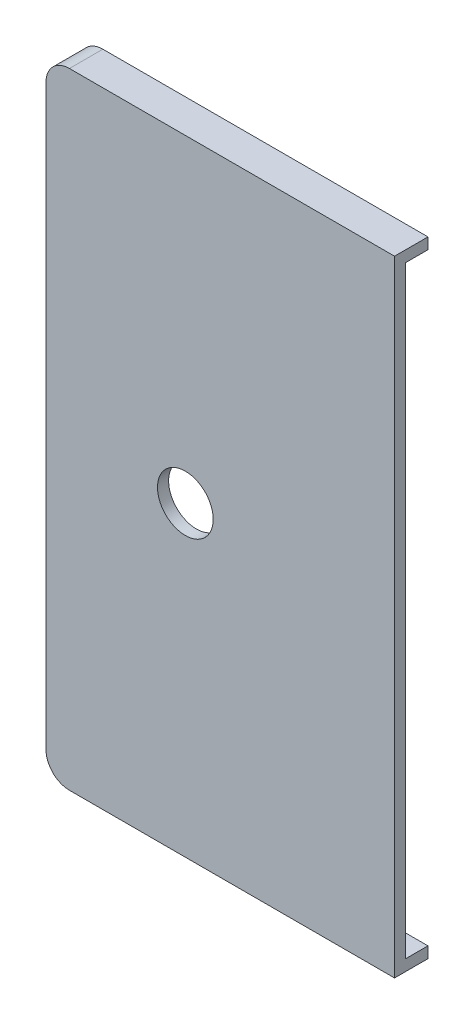
SolidWorks part; units mm, degrees
ref_plane "Front Plane" through (0, 0, 0) normal (0, 0, 1) x (1, 0, 0)
ref_plane "Top Plane" through (0, 0, 0) normal (0, 1, 0) x (1, 0, 0)
ref_plane "Right Plane" through (0, 0, 0) normal (1, 0, 0) x (0, 0, -1)
sketch "Sketch1" plane through (0, 0, 0) normal (0, 0, 1) x (1, 0, 0)
  line L4 (657.3112, -1230.231) -> (657.3112, -1334.011)
  line L5 (661.5112, -1338.211) -> (719.8512, -1338.211)
  line L7 (719.8512, -1226.031) -> (661.5112, -1226.031)
  line L8 (659.3112, -1230.231) -> (659.3112, -1334.011)
  line L9 (661.5112, -1336.211) -> (769.8512, -1336.211)
  line L10 (772.0512, -1334.011) -> (772.0512, -1230.231)
  line L11 (769.8512, -1228.031) -> (661.5112, -1228.031)
  line L12 (659.3112, -1230.231) -> (659.3112, -1334.011)
  line L13 (661.5112, -1336.211) -> (719.8512, -1336.211)
  line L15 (719.8512, -1228.031) -> (661.5112, -1228.031)
  line L16 (719.8512, -1327.661) -> (719.8512, -1261.621) construction
  line L17 (719.8512, -1327.661) -> (719.8512, -1261.621)
  line L18 (719.8512, -1261.621) -> (719.8512, -1226.031)
  line L19 (719.8512, -1327.661) -> (719.8512, -1338.211)
  line L20 (769.8512, -1226.031) -> (661.5112, -1226.031) construction
  line L21 (769.8512, -1228.031) -> (661.5112, -1228.031) construction
  line L22 (661.5112, -1336.211) -> (769.8512, -1336.211) construction
  line L23 (661.5112, -1338.211) -> (769.8512, -1338.211) construction
  line L24 (772.0512, -1334.011) -> (772.0512, -1230.231) construction
  line L25 (774.0512, -1334.011) -> (774.0512, -1230.231) construction
  arc A4 (657.3112, -1334.011) -> (661.5112, -1338.211) centre (661.5112, -1334.011) ccw
  arc A7 (661.5112, -1226.031) -> (657.3112, -1230.231) centre (661.5112, -1230.231) ccw
  arc A8 (659.3112, -1334.011) -> (661.5112, -1336.211) centre (661.5112, -1334.011) ccw
  arc A9 (769.8512, -1336.211) -> (772.0512, -1334.011) centre (769.8512, -1334.011) ccw
  arc A10 (772.0512, -1230.231) -> (769.8512, -1228.031) centre (769.8512, -1230.231) ccw
  arc A11 (661.5112, -1228.031) -> (659.3112, -1230.231) centre (661.5112, -1230.231) ccw
  arc A12 (659.3112, -1334.011) -> (661.5112, -1336.211) centre (661.5112, -1334.011) ccw
  arc A15 (661.5112, -1228.031) -> (659.3112, -1230.231) centre (661.5112, -1230.231) ccw
  arc A20 (774.0512, -1230.231) -> (769.8512, -1226.031) centre (769.8512, -1230.231) ccw construction
  arc A21 (772.0512, -1230.231) -> (769.8512, -1228.031) centre (769.8512, -1230.231) ccw construction
  arc A22 (769.8512, -1338.211) -> (774.0512, -1334.011) centre (769.8512, -1334.011) ccw construction
  arc A23 (769.8512, -1336.211) -> (772.0512, -1334.011) centre (769.8512, -1334.011) ccw construction
extrude "Boss-Extrude1" add sketch "Sketch1" along normal blind 2 contours A15 L15 L18 L7 A7 L4 A4 L5 L19 L13 A12 L12 | L15 A15 L12 A12 L13 L19 L17 L18 region at (659.4496, -1228.1693, 0) region at (689.5907, -1282.121, 0)
extrude "Boss-Extrude2" add sketch "Sketch1<3>" against normal blind 4 contours A15 L15 L18 L7 A7 L4 A4 L5 L19 L13 A12 L12 region at (659.4496, -1228.1693, 0)
sketch "Sketch1<3>" plane through (0, 0, 0) normal (0, 0, 1) x (1, 0, 0) same geometry as "Sketch1"
sketch "Sketch2" plane through (0, 0, 2) normal (0, 0, 1) x (1, 0, 0)
  line L0 (657.3112, -1283.211) -> (682.3112, -1283.211)
  line L1 (657.3112, -1230.231) -> (657.3112, -1334.011) construction
  line L2 (682.3112, -1283.211) -> (682.3112, -1338.211)
  line L3 (661.5112, -1338.211) -> (719.8512, -1338.211) construction
  circle A0 centre (682.3112, -1283.211) radius 5
  dimension "D3" = 10
  dimension "D1" = 55
  dimension "D2" = 25
extrude "Cut-Extrude1" cut sketch "Sketch2" against normal up to surface (2 mm away) contours L2 A0 L0 | L0 A0 L2 region at (683.0186, -1282.5036, 2) region at (680.1892, -1285.333, 2) up to face at (680.0727, -1282.121, 0)
equation "\"C\"=0.2"
equation "\"D1@Sketch1\"=\"C\""
equation "\"T\"=2"
equation "\"D2@Sketch1\"=\"T\""
equation "\"D1@Boss-Extrude1\"=\"T\""
equation "\"HANG\"=4"
equation "\"D2@Boss-Extrude1\"=\"HANG\""
equation "\"D1@Boss-Extrude2\"=\"HANG\""
equation "\"OFF1\"=55"
equation "\"OFF2\"=25"
equation "\"D2@Sketch2\"=\"OFF2\""
equation "\"HOLED\"= 10"
equation "\"D3@Sketch2\"=\"HOLED\""
equation "\"D1@Sketch2\"=\"OFF1\""
